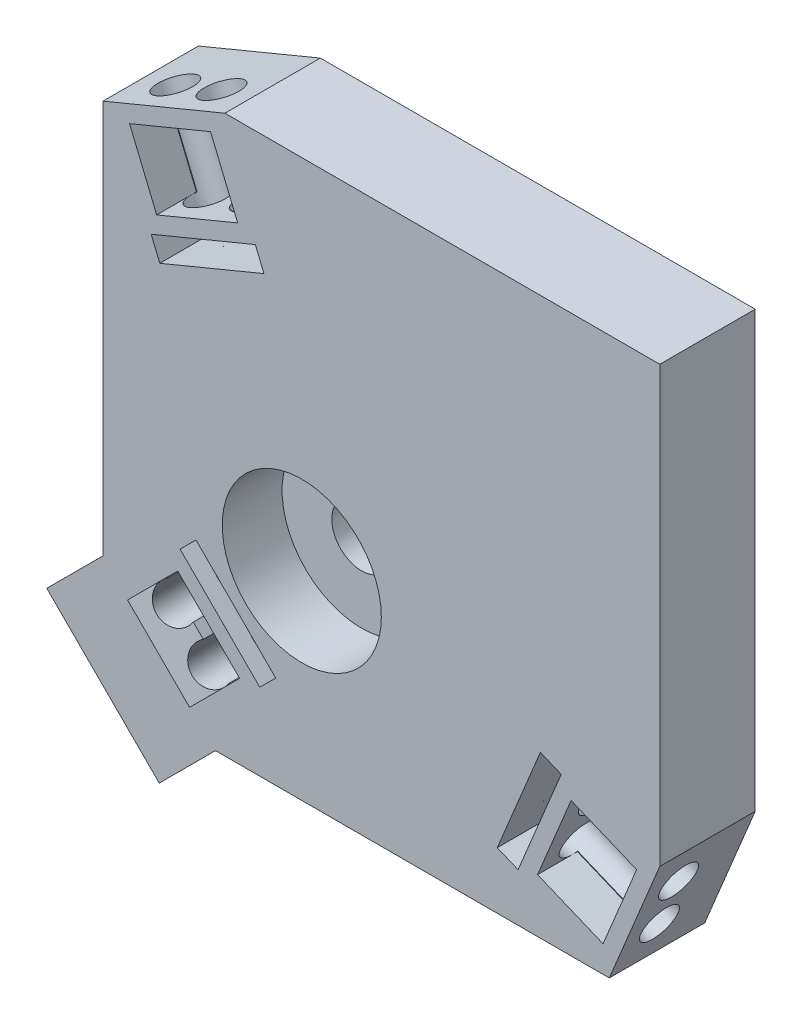
SolidWorks part; units mm, degrees
material "3D Printer - Undefined Plastic"
ref_plane "Front Plane" through (0, 0, 0) normal (0, 0, 1) x (1, 0, 0)
ref_plane "Top Plane" through (0, 0, 0) normal (0, 1, 0) x (1, 0, 0)
ref_plane "Right Plane" through (0, 0, 0) normal (1, 0, 0) x (0, 0, -1)
sketch "Sketch1" plane through (0, 0, 0) normal (0, 0, 1) x (1, 0, 0)
  line L0 (0, 44.45) -> (9.7313, 44.45) construction
  line L1 (9.7313, 44.45) -> (44.45, 9.7313) construction
  line L2 (44.45, 9.7313) -> (44.45, 0) construction
  line L3 (44.45, 0) -> (0, 0)
  line L4 (0, 0) -> (0, 44.45)
  line L5 (0, 8.9803) -> (-4.4901, 4.4901)
  line L6 (-4.4901, 4.4901) -> (4.4901, -4.4901)
  line L7 (4.4901, -4.4901) -> (8.9803, 0)
  line L8 (9.7313, 44.45) -> (0, 40.4191)
  line L9 (34.8588, 8.0037) -> (0, 22.4426) construction
  line L10 (3.8462, 33.1367) -> (12.1611, 36.5808)
  line L11 (3.8462, 33.1367) -> (4.535, 31.4737)
  line L12 (4.535, 31.4737) -> (12.85, 34.9179)
  line L13 (12.1611, 36.5808) -> (12.85, 34.9179)
  line L14 (3.8462, 33.1367) -> (12.85, 34.9179) construction
  line L15 (4.535, 31.4737) -> (12.1611, 36.5808) construction
  line L16 (36.5808, 12.1611) -> (34.9179, 12.85)
  line L17 (36.5808, 12.1611) -> (33.1367, 3.8462)
  line L18 (33.1367, 3.8462) -> (31.4737, 4.535)
  line L19 (34.9179, 12.85) -> (31.4737, 4.535)
  line L20 (36.5808, 12.1611) -> (31.4737, 4.535) construction
  line L21 (33.1367, 3.8462) -> (34.9179, 12.85) construction
  line L22 (6.1518, 12.5158) -> (7.4246, 13.7886)
  line L23 (0, 44.45) -> (0, 54.1813) construction
  line L24 (0, 54.1813) -> (9.7313, 44.45) construction
  line L25 (44.45, 9.7313) -> (54.1813, 0) construction
  line L26 (54.1813, 0) -> (44.45, 0) construction
  line L27 (4.0309, 44.45) -> (4.8657, 42.4346) construction
  line L28 (6.1518, 12.5158) -> (12.5158, 6.1518)
  line L29 (7.4246, 13.7886) -> (13.7886, 7.4246)
  line L30 (12.5158, 6.1518) -> (13.7886, 7.4246)
  line L31 (6.1518, 12.5158) -> (13.7886, 7.4246) construction
  line L32 (7.4246, 13.7886) -> (12.5158, 6.1518) construction
  line L33 (4.4336, 4.4336) -> (6.4347, 6.4347) construction
  line L34 (0, 54.1813) -> (4.0309, 44.45) construction
  line L35 (54.1813, 0) -> (42.4346, 4.8657) construction
  line L36 (9.9702, 9.9702) -> (15.8693, 15.8693) construction
  line L37 (44.45, 9.7313) -> (40.4191, 0)
  line L38 (5.9609, 10.9107) -> (10.9107, 5.9609)
  line L39 (5.9609, 10.9107) -> (1.9587, 6.9084)
  line L40 (10.9107, 5.9609) -> (6.9084, 1.9587)
  line L41 (1.9587, 6.9084) -> (6.9084, 1.9587)
  line L42 (5.9609, 10.9107) -> (6.9084, 1.9587) construction
  line L43 (10.9107, 5.9609) -> (1.9587, 6.9084) construction
  line L44 (37.3715, 10.7512) -> (34.6927, 4.2841)
  line L45 (37.3715, 10.7512) -> (42.6006, 8.5853)
  line L46 (34.6927, 4.2841) -> (39.9219, 2.1181)
  line L47 (42.6006, 8.5853) -> (39.9219, 2.1181)
  line L48 (37.3715, 10.7512) -> (39.9219, 2.1181) construction
  line L49 (34.6927, 4.2841) -> (42.6006, 8.5853) construction
  line L50 (2.1181, 39.9219) -> (8.5853, 42.6006)
  line L51 (2.1181, 39.9219) -> (4.2841, 34.6927)
  line L52 (8.5853, 42.6006) -> (10.7512, 37.3715)
  line L53 (4.2841, 34.6927) -> (10.7512, 37.3715)
  line L54 (2.1181, 39.9219) -> (10.7512, 37.3715) construction
  line L55 (8.5853, 42.6006) -> (4.2841, 34.6927) construction
  line L56 (6.4347, 6.4347) -> (8.4358, 8.4358) construction
  line L57 (8.4358, 8.4358) -> (9.3338, 9.3338) construction
  line L58 (9.3338, 9.3338) -> (9.9702, 9.9702) construction
  line L59 (42.4346, 4.8657) -> (41.2612, 5.3517) construction
  line L60 (41.2612, 5.3517) -> (38.6467, 6.4347) construction
  line L61 (38.6467, 6.4347) -> (36.0321, 7.5177) construction
  line L62 (36.0321, 7.5177) -> (34.8588, 8.0037) construction
  line L63 (8.0037, 34.8588) -> (8.3481, 34.0273) construction
  line L64 (7.5177, 36.0321) -> (8.0037, 34.8588) construction
  line L65 (8.3481, 34.0273) -> (15.8693, 15.8693) construction
  line L66 (0, 0) -> (4.4336, 4.4336) construction
  line L67 (5.3517, 41.2612) -> (7.5177, 36.0321) construction
  line L68 (4.8657, 42.4346) -> (5.3517, 41.2612) construction
  line L69 (6.4347, 6.4347) -> (38.6467, 6.4347) construction
  line L70 (9.7313, 44.45) -> (44.45, 44.45)
  line L71 (44.45, 44.45) -> (44.45, 9.7313)
  circle A0 centre (15.8693, 15.8693) radius 6.35
  arc A1 (4.8657, 49.3157) -> (0, 47.3002) centre (0, 54.1813) cw construction
  arc A2 (49.3157, 4.8657) -> (47.3002, 0) centre (54.1813, 0) ccw construction
  arc A3 (-4.4901, 4.4901) -> (0, 15.3303) centre (-15.3303, 15.3303) ccw
  arc A4 (4.4901, -4.4901) -> (15.3303, 0) centre (15.3303, -15.3303) cw
  circle A5 centre (15.8693, 15.8693) radius 2.3812
  point P15 (8.3481, 34.0273)
  point P22 (34.0273, 8.3481)
  point P26 (9.9702, 9.9702)
  point P38 (47.824, 2.6333)
  point P41 (2.6333, 47.824)
  point P44 (15.8693, 15.8693)
  point P49 (6.4347, 6.4347)
  point P50 (38.6467, 6.4347)
  point P51 (6.4347, 38.6467)
  dimension "D4" = 12.7
  dimension "D9" = 4.7625
  dimension "D1" = 9
  dimension "D2" = 1.8
  dimension "D6" = 12.7
  dimension "D11" = 1.27
  dimension "D12" = 1.27
  dimension "D13" = 7
  dimension "D10" = 10
  dimension "D3" = 10
  dimension "D5" = 15
  dimension "D7" = 44.45
extrude "Boss-Extrude1" add sketch "Sketch1" along normal blind 7.62 contours L4 L3 L2 L1 L0 A0 L30 L28 L22 L29 L19 L16 L17 L18 L10 L13 L12 L11 | L13 L10 L11 L12 | A0 | L28 L30 L29 L22 | L5 L6 L4 | L6 L7 L3 | L16 L19 L18 L17 | L4 L41 L3 L40 L38 L39 | L41 L4 L3 | L51 L53 L52 L50 | L47 L45 L44 L46 region at (23.1995, 23.1995, 0) region at (4.4901, -1.4967, 0) region at (-1.4967, 4.4901, 0) region at (8.3481, 34.0273, 0) region at (34.0273, 8.3481, 0) region at (9.9702, 9.9702, 0) region at (6.4347, 6.4347, 0) region at (38.6467, 6.4347, 0) region at (6.4347, 38.6467, 0) region at (9.699, 15.8693, 0)
extrude "Magnet Hole" cut sketch "Sketch1<3>" against normal blind 4.7752 from surface contours A0 region at (9.699, 15.8693, 0) starting at face at (16.4479, 16.4479, 7.62)
sketch "Sketch1<3>" plane through (0, 0, 0) normal (0, 0, 1) x (1, 0, 0) same geometry as "Sketch1"
extrude "Cut-Extrude2" cut sketch "Sketch1<4>" against normal blind 5.6 from surface contours L16 L19 L18 L17 | L28 L30 L29 L22 | L13 L12 L11 L10 region at (34.0273, 8.3481, 0) region at (9.9702, 9.9702, 0) starting at face at (22.2193, 15.8693, 7.62)
sketch "Sketch1<4>" plane through (0, 0, 0) normal (0, 0, 1) x (1, 0, 0) same geometry as "Sketch1"
hole_wizard "Ø3.0mm Dowel Hole1" positions "3DSketch1" profile "Sketch3" hole size "Ø3.0" standard "ANSI Metric"
sketch3d "3DSketch1"
  line L4 (-1.4142, 1.4142, 4.87) -> (1.4142, -1.4142, 4.87) construction
  line L6 (0, 0, 7.62) -> (0, 0, 4.87) construction
  line L7 (-4.4901, 4.4901, 7.62) -> (4.4901, -4.4901, 7.62) construction
  line L25 (42.4346, 4.8657, 7.62) -> (42.4346, 4.8657, 4.87) construction
  line L26 (44.45, 9.7313, 7.62) -> (40.4191, 0, 7.62) construction
  line L29 (4.8657, 42.4346, 4.87) -> (4.8657, 42.4346, 7.62) construction
  line L30 (9.7313, 44.45, 7.62) -> (0, 40.4191, 7.62) construction
  line L31 (6.7134, 43.1999, 4.87) -> (3.0179, 41.6692, 4.87) construction
  line L33 (41.6692, 3.0179, 4.87) -> (43.1999, 6.7134, 4.87) construction
  point P4 (-1.4142, 1.4142, 4.87)
  point P6 (1.4142, -1.4142, 4.87)
  point P101 (43.1999, 6.7134, 4.87)
  point P103 (41.6692, 3.0179, 4.87)
  point P105 (3.0179, 41.6692, 4.87)
  point P107 (6.7134, 43.1999, 4.87)
  dimension "D1" = 2.75
  dimension "D2" = 2
sketch "Sketch3" plane through (-1.4142, 1.4142, 4.87) normal (0, 0, 1) x (0.7071, -0.7071, 0)
  line L0 (0, 0) -> (0, 10.0076)
  line L1 (0, 10.0076) -> (1.5, 9.1063)
  line L2 (1.5, 9.1063) -> (1.5, 0)
  line L5 (1.5, 0) -> (0, 0)
  line L10 (0, 10.0076) -> (-1.5, 9.1063) construction
  line L11 (0, -6.35) -> (0, 107.95) construction
  dimension "Hole Dia." = 3
  dimension "Hole Depth" = 10.0076
  dimension "Drill Angle" = 118
hole_wizard "Ø3.0mm Dowel Hole2" positions "Sketch7" profile "Sketch8" hole size "Ø3.0" standard "ANSI Metric" end condition up to next
sketch "Sketch7" plane through (0, 0, 0) normal (-0.7071, -0.7071, 0) x (-0.7071, 0.7071, 0)
  point P0 (-2, -4.87)
  point P3 (2, -4.87)
sketch "Sketch8" plane through (1.4142, -1.4142, 4.87) normal (0, 0, 1) x (0.7071, -0.7071, 0)
  line L0 (0, 0) -> (0, 13.2)
  line L1 (0, 13.2) -> (1.5, 13.2)
  line L2 (1.5, 13.2) -> (1.5, 0)
  line L5 (1.5, 0) -> (0, 0)
  line L11 (0, -6.35) -> (0, 107.95) construction
  dimension "Thru Hole Dia." = 3
  dimension "Thru Hole Depth" = 13.2
sketch "Sketch4" plane through (0, 0, 0) normal (0, 0, -1) x (-1, 0, 0)
  line L0 (-44.45, 9.7313) -> (-44.45, -4.4901)
  line L1 (-44.45, -4.4901) -> (4.4901, -4.4901)
  line L2 (4.4901, -4.4901) -> (4.4901, 44.45)
  line L3 (4.4901, 44.45) -> (-9.7313, 44.45)
  line L4 (-9.7313, 44.45) -> (0, 40.4191) construction
  line L5 (0, 8.9803) -> (0, 40.4191) construction
  line L6 (0, 8.9803) -> (4.4901, 4.4901) construction
  line L7 (4.4901, 4.4901) -> (-4.4901, -4.4901) construction
  line L8 (-4.4901, -4.4901) -> (-8.9803, 0) construction
  line L9 (-40.4191, 0) -> (-8.9803, 0) construction
  line L10 (-44.45, 9.7313) -> (-40.4191, 0) construction
  line L11 (-9.7313, 44.45) -> (0, 40.4191)
  line L12 (0, 8.9803) -> (0, 40.4191)
  line L13 (0, 8.9803) -> (4.4901, 4.4901)
  line L14 (4.4901, 4.4901) -> (-4.4901, -4.4901)
  line L15 (-4.4901, -4.4901) -> (-8.9803, 0)
  line L16 (-40.4191, 0) -> (-8.9803, 0)
  line L17 (-44.45, 9.7313) -> (-40.4191, 0)
  point P3 (-4.4901, -4.4901)
  point P8 (4.4901, 4.4901)
  line M4 (-44.45, 9.7313) -> (-40.4191, 0)
  line M5 (-40.4191, 0) -> (-8.9803, 0)
  line M6 (-8.9803, 0) -> (-4.4901, -4.4901)
  line M7 (-4.4901, -4.4901) -> (4.4901, 4.4901)
  line M8 (4.4901, 4.4901) -> (0, 8.9803)
  line M9 (0, 8.9803) -> (0, 40.4191)
  line M10 (0, 40.4191) -> (-9.7313, 44.45)
extrude "Boss-Extrude2" [suppressed] add sketch "Sketch4" against normal blind 2.54 contours L0 L1 M6 M5 M4 | L1 L2 M7 | L2 L3 M10 M9 M8
extrude "Cut-Extrude3" cut sketch "Sketch1<5>" against normal blind 3.175 from surface contours L39 L41 L40 L38 | L51 L53 L52 L50 | L45 L47 L46 L44 region at (6.4347, 6.4347, 0) region at (6.4347, 38.6467, 0) starting at face at (34.0273, 8.3481, 7.62)
sketch "Sketch1<5>" plane through (0, 0, 0) normal (0, 0, 1) x (1, 0, 0) same geometry as "Sketch1"
equation "\"D3@Sketch1\"=\"D10@Sketch1\""
equation "\"D5@Sketch1\"=1.5*\"D10@Sketch1\""
